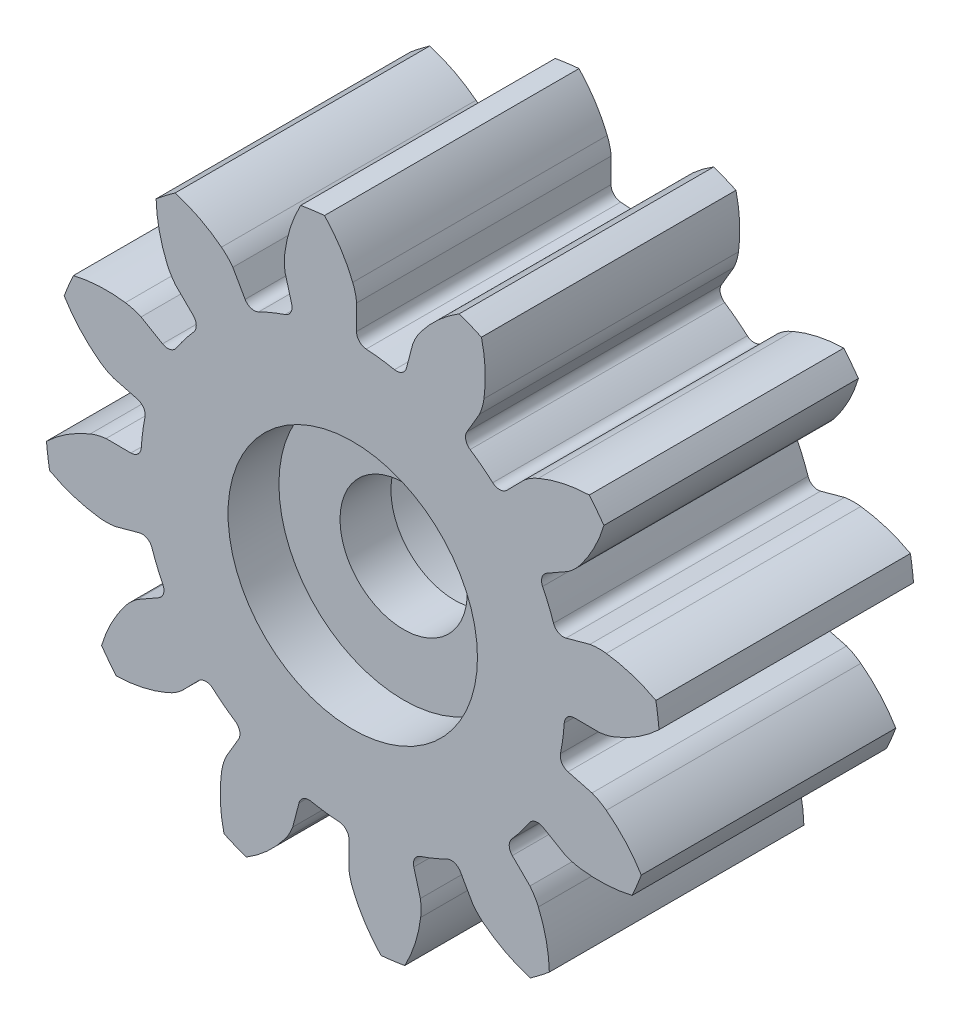
SolidWorks part; units mm, degrees
ref_plane "Front Plane" through (0, 0, 0) normal (0, 0, 1) x (1, 0, 0)
ref_plane "Top Plane" through (0, 0, 0) normal (0, 1, 0) x (1, 0, 0)
ref_plane "Right Plane" through (0, 0, 0) normal (1, 0, 0) x (0, 0, -1)
sketch "Sketch1" plane through (0, 0, 0) normal (0, 0, 1) x (1, 0, 0)
  line L48 (-1.3289, 4.6605) -> (-1.1999, 4.1898)
  line L49 (-2.1142, 3.8111) -> (-2.3558, 4.2352)
  line L50 (-3.4812, 3.3716) -> (-3.134, 3.0285)
  line L51 (-3.7365, 2.2434) -> (-4.1577, 2.4899)
  line L52 (-4.7006, 1.1794) -> (-4.2284, 1.0558)
  line L53 (-4.3576, 0.0746) -> (-4.8457, 0.0774)
  line L54 (-4.6605, -1.3289) -> (-4.1898, -1.1999)
  line L55 (-3.8111, -2.1142) -> (-4.2352, -2.3558)
  line L56 (-3.3716, -3.4812) -> (-3.0285, -3.134)
  line L57 (-2.2434, -3.7365) -> (-2.4899, -4.1577)
  line L58 (-1.1794, -4.7006) -> (-1.0558, -4.2284)
  line L59 (-0.0746, -4.3576) -> (-0.0774, -4.8457)
  line L60 (1.3289, -4.6605) -> (1.1999, -4.1898)
  line L61 (2.1142, -3.8111) -> (2.3558, -4.2352)
  line L62 (3.4812, -3.3716) -> (3.134, -3.0285)
  line L63 (3.7365, -2.2434) -> (4.1577, -2.4899)
  line L64 (4.7006, -1.1794) -> (4.2284, -1.0558)
  line L65 (4.3576, -0.0746) -> (4.8457, -0.0774)
  line L66 (4.6605, 1.3289) -> (4.1898, 1.1999)
  line L67 (3.8111, 2.1142) -> (4.2352, 2.3558)
  line L68 (3.3716, 3.4812) -> (3.0285, 3.134)
  line L69 (2.2434, 3.7365) -> (2.4899, 4.1577)
  line L70 (1.1794, 4.7006) -> (1.0558, 4.2284)
  line L71 (0.0746, 4.3576) -> (0.0774, 4.8457)
  circle A0 centre (0, 0) radius 2.45
  arc A192 (0.0002, 5.1569) -> (-0.5543, 6.0169) centre (-2.5558, 4.1176) ccw
  arc A193 (-0.5543, 6.0169) -> (-1.0218, 5.9553) centre (0, 0) ccw
  arc A194 (-1.0218, 5.9553) -> (-1.3349, 4.9811) centre (1.403, 4.6388) ccw
  arc A195 (-1.3349, 4.9811) -> (-1.3289, 4.6605) centre (-0.2176, 4.8414) ccw
  arc A196 (-1.3304, 3.9445) -> (-1.1999, 4.1898) centre (-1.3951, 4.1363) ccw
  arc A197 (-1.3304, 3.9445) -> (-1.8484, 3.7299) centre (0, 0) ccw
  arc A198 (-2.1142, 3.8111) -> (-1.8484, 3.7299) centre (-1.9383, 3.9113) ccw
  arc A199 (-2.3558, 4.2352) -> (-2.5783, 4.4661) centre (-3.2695, 3.5772) ccw
  arc A200 (-2.5783, 4.4661) -> (-3.4885, 4.9336) centre (-4.2721, 2.288) ccw
  arc A201 (-3.4885, 4.9336) -> (-3.8626, 4.6465) centre (0, 0) ccw
  arc A202 (-3.8626, 4.6465) -> (-3.6466, 3.6463) centre (-1.1044, 4.7188) ccw
  arc A203 (-3.6466, 3.6463) -> (-3.4812, 3.3716) centre (-2.6091, 4.084) ccw
  arc A204 (-3.1244, 2.7508) -> (-3.134, 3.0285) centre (-3.2763, 2.8846) ccw
  arc A205 (-3.1244, 2.7508) -> (-3.4657, 2.306) centre (0, 0) ccw
  arc A206 (-3.7365, 2.2434) -> (-3.4657, 2.306) centre (-3.6343, 2.4181) ccw
  arc A207 (-4.1577, 2.4899) -> (-4.4659, 2.5786) centre (-4.6201, 1.4632) ccw
  arc A208 (-4.4659, 2.5786) -> (-5.4879, 2.5284) centre (-4.8438, -0.1546) ccw
  arc A209 (-5.4879, 2.5284) -> (-5.6684, 2.0927) centre (0, 0) ccw
  arc A210 (-5.6684, 2.0927) -> (-4.9812, 1.3345) centre (-3.3158, 3.5344) ccw
  arc A211 (-4.9812, 1.3345) -> (-4.7006, 1.1794) centre (-4.3015, 2.2323) ccw
  arc A212 (-4.0812, 0.8201) -> (-4.2284, 1.0558) centre (-4.2797, 0.86) ccw
  arc A213 (-4.0812, 0.8201) -> (-4.1544, 0.2642) centre (0, 0) ccw
  arc A214 (-4.3576, 0.0746) -> (-4.1544, 0.2642) centre (-4.3564, 0.277) ccw
  arc A215 (-4.8457, 0.0774) -> (-5.1569, 0.0002) centre (-4.7327, -1.0429) ccw
  arc A216 (-5.1569, 0.0002) -> (-6.0169, -0.5543) centre (-4.1176, -2.5558) ccw
  arc A217 (-6.0169, -0.5543) -> (-5.9553, -1.0218) centre (0, 0) ccw
  arc A218 (-5.9553, -1.0218) -> (-4.9811, -1.3349) centre (-4.6388, 1.403) ccw
  arc A219 (-4.9811, -1.3349) -> (-4.6605, -1.3289) centre (-4.8414, -0.2176) ccw
  arc A220 (-3.9445, -1.3304) -> (-4.1898, -1.1999) centre (-4.1363, -1.3951) ccw
  arc A221 (-3.9445, -1.3304) -> (-3.7299, -1.8484) centre (0, 0) ccw
  arc A222 (-3.8111, -2.1142) -> (-3.7299, -1.8484) centre (-3.9113, -1.9383) ccw
  arc A223 (-4.2352, -2.3558) -> (-4.4661, -2.5783) centre (-3.5772, -3.2695) ccw
  arc A224 (-4.4661, -2.5783) -> (-4.9336, -3.4885) centre (-2.288, -4.2721) ccw
  arc A225 (-4.9336, -3.4885) -> (-4.6465, -3.8626) centre (0, 0) ccw
  arc A226 (-4.6465, -3.8626) -> (-3.6463, -3.6466) centre (-4.7188, -1.1044) ccw
  arc A227 (-3.6463, -3.6466) -> (-3.3716, -3.4812) centre (-4.084, -2.6091) ccw
  arc A228 (-2.7508, -3.1244) -> (-3.0285, -3.134) centre (-2.8846, -3.2763) ccw
  arc A229 (-2.7508, -3.1244) -> (-2.306, -3.4657) centre (0, 0) ccw
  arc A230 (-2.2434, -3.7365) -> (-2.306, -3.4657) centre (-2.4181, -3.6343) ccw
  arc A231 (-2.4899, -4.1577) -> (-2.5786, -4.4659) centre (-1.4632, -4.6201) ccw
  arc A232 (-2.5786, -4.4659) -> (-2.5284, -5.4879) centre (0.1546, -4.8438) ccw
  arc A233 (-2.5284, -5.4879) -> (-2.0927, -5.6684) centre (0, 0) ccw
  arc A234 (-2.0927, -5.6684) -> (-1.3345, -4.9812) centre (-3.5344, -3.3158) ccw
  arc A235 (-1.3345, -4.9812) -> (-1.1794, -4.7006) centre (-2.2323, -4.3015) ccw
  arc A236 (-0.8201, -4.0812) -> (-1.0558, -4.2284) centre (-0.86, -4.2797) ccw
  arc A237 (-0.8201, -4.0812) -> (-0.2642, -4.1544) centre (0, 0) ccw
  arc A238 (-0.0746, -4.3576) -> (-0.2642, -4.1544) centre (-0.277, -4.3564) ccw
  arc A239 (-0.0774, -4.8457) -> (-0.0002, -5.1569) centre (1.0429, -4.7327) ccw
  arc A240 (-0.0002, -5.1569) -> (0.5543, -6.0169) centre (2.5558, -4.1176) ccw
  arc A241 (0.5543, -6.0169) -> (1.0218, -5.9553) centre (0, 0) ccw
  arc A242 (1.0218, -5.9553) -> (1.3349, -4.9811) centre (-1.403, -4.6388) ccw
  arc A243 (1.3349, -4.9811) -> (1.3289, -4.6605) centre (0.2176, -4.8414) ccw
  arc A244 (1.3304, -3.9445) -> (1.1999, -4.1898) centre (1.3951, -4.1363) ccw
  arc A245 (1.3304, -3.9445) -> (1.8484, -3.7299) centre (0, 0) ccw
  arc A246 (2.1142, -3.8111) -> (1.8484, -3.7299) centre (1.9383, -3.9113) ccw
  arc A247 (2.3558, -4.2352) -> (2.5783, -4.4661) centre (3.2695, -3.5772) ccw
  arc A248 (2.5783, -4.4661) -> (3.4885, -4.9336) centre (4.2721, -2.288) ccw
  arc A249 (3.4885, -4.9336) -> (3.8626, -4.6465) centre (0, 0) ccw
  arc A250 (3.8626, -4.6465) -> (3.6466, -3.6463) centre (1.1044, -4.7188) ccw
  arc A251 (3.6466, -3.6463) -> (3.4812, -3.3716) centre (2.6091, -4.084) ccw
  arc A252 (3.1244, -2.7508) -> (3.134, -3.0285) centre (3.2763, -2.8846) ccw
  arc A253 (3.1244, -2.7508) -> (3.4657, -2.306) centre (0, 0) ccw
  arc A254 (3.7365, -2.2434) -> (3.4657, -2.306) centre (3.6343, -2.4181) ccw
  arc A255 (4.1577, -2.4899) -> (4.4659, -2.5786) centre (4.6201, -1.4632) ccw
  arc A256 (4.4659, -2.5786) -> (5.4879, -2.5284) centre (4.8438, 0.1546) ccw
  arc A257 (5.4879, -2.5284) -> (5.6684, -2.0927) centre (0, 0) ccw
  arc A258 (5.6684, -2.0927) -> (4.9812, -1.3345) centre (3.3158, -3.5344) ccw
  arc A259 (4.9812, -1.3345) -> (4.7006, -1.1794) centre (4.3015, -2.2323) ccw
  arc A260 (4.0812, -0.8201) -> (4.2284, -1.0558) centre (4.2797, -0.86) ccw
  arc A261 (4.0812, -0.8201) -> (4.1544, -0.2642) centre (0, 0) ccw
  arc A262 (4.3576, -0.0746) -> (4.1544, -0.2642) centre (4.3564, -0.277) ccw
  arc A263 (4.8457, -0.0774) -> (5.1569, -0.0002) centre (4.7327, 1.0429) ccw
  arc A264 (5.1569, -0.0002) -> (6.0169, 0.5543) centre (4.1176, 2.5558) ccw
  arc A265 (6.0169, 0.5543) -> (5.9553, 1.0218) centre (0, 0) ccw
  arc A266 (5.9553, 1.0218) -> (4.9811, 1.3349) centre (4.6388, -1.403) ccw
  arc A267 (4.9811, 1.3349) -> (4.6605, 1.3289) centre (4.8414, 0.2176) ccw
  arc A268 (3.9445, 1.3304) -> (4.1898, 1.1999) centre (4.1363, 1.3951) ccw
  arc A269 (3.9445, 1.3304) -> (3.7299, 1.8484) centre (0, 0) ccw
  arc A270 (3.8111, 2.1142) -> (3.7299, 1.8484) centre (3.9113, 1.9383) ccw
  arc A271 (4.2352, 2.3558) -> (4.4661, 2.5783) centre (3.5772, 3.2695) ccw
  arc A272 (4.4661, 2.5783) -> (4.9336, 3.4885) centre (2.288, 4.2721) ccw
  arc A273 (4.9336, 3.4885) -> (4.6465, 3.8626) centre (0, 0) ccw
  arc A274 (4.6465, 3.8626) -> (3.6463, 3.6466) centre (4.7188, 1.1044) ccw
  arc A275 (3.6463, 3.6466) -> (3.3716, 3.4812) centre (4.084, 2.6091) ccw
  arc A276 (2.7508, 3.1244) -> (3.0285, 3.134) centre (2.8846, 3.2763) ccw
  arc A277 (2.7508, 3.1244) -> (2.306, 3.4657) centre (0, 0) ccw
  arc A278 (2.2434, 3.7365) -> (2.306, 3.4657) centre (2.4181, 3.6343) ccw
  arc A279 (2.4899, 4.1577) -> (2.5786, 4.4659) centre (1.4632, 4.6201) ccw
  arc A280 (2.5786, 4.4659) -> (2.5284, 5.4879) centre (-0.1546, 4.8438) ccw
  arc A281 (2.5284, 5.4879) -> (2.0927, 5.6684) centre (0, 0) ccw
  arc A282 (2.0927, 5.6684) -> (1.3345, 4.9812) centre (3.5344, 3.3158) ccw
  arc A283 (1.3345, 4.9812) -> (1.1794, 4.7006) centre (2.2323, 4.3015) ccw
  arc A284 (0.8201, 4.0812) -> (1.0558, 4.2284) centre (0.86, 4.2797) ccw
  arc A285 (0.8201, 4.0812) -> (0.2642, 4.1544) centre (0, 0) ccw
  arc A286 (0.0746, 4.3576) -> (0.2642, 4.1544) centre (0.277, 4.3564) ccw
  arc A287 (0.0774, 4.8457) -> (0.0002, 5.1569) centre (-1.0429, 4.7327) ccw
  dimension "D1" = 4.9
extrude "Boss-Extrude1" add sketch "Sketch1" along normal blind 1 and the other way blind 4
sketch "Sketch2" plane through (0, 0, -4) normal (0, 0, -1) x (-1, 0, 0)
  circle A0 centre (0, 0) radius 2.45
  circle A2 centre (0, 0) radius 1.25
  circle A4 centre (0, 0) radius 2.45 construction
  dimension "D2" = 2.5
extrude "Boss-Extrude2" add sketch "Sketch2" against normal blind 1 from offset 3 offset against normal yes
